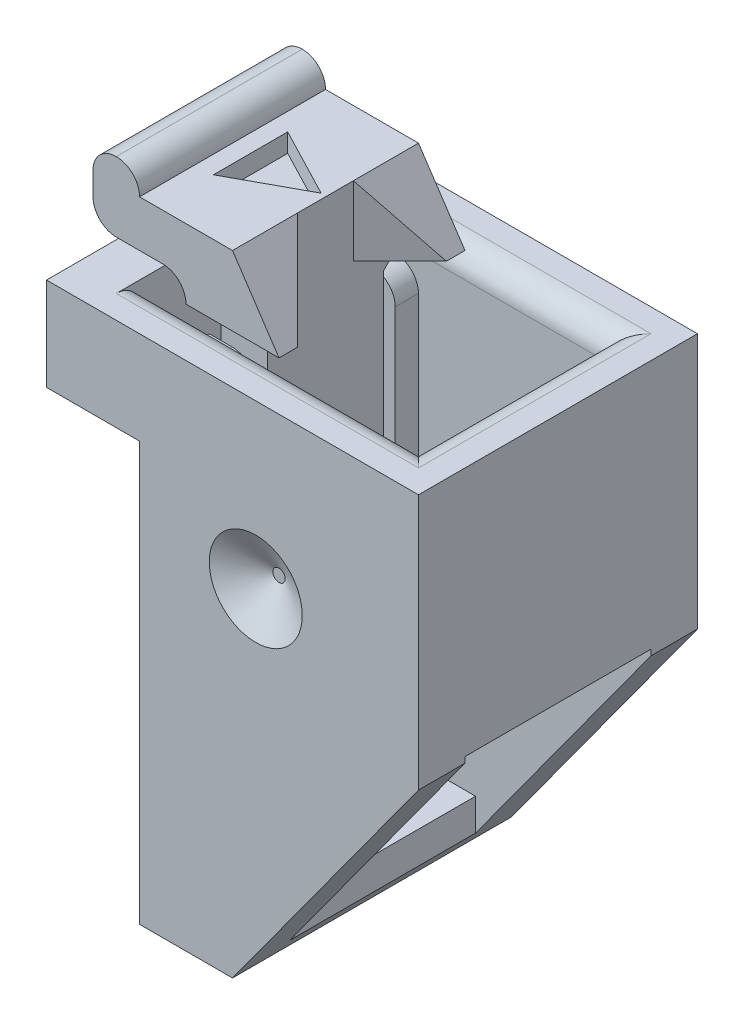
SolidWorks part; units mm, degrees
ref_plane "Front Plane" through (0, 0, 0) normal (0, 0, 1) x (1, 0, 0)
ref_plane "Top Plane" through (0, 0, 0) normal (0, 1, 0) x (1, 0, 0)
ref_plane "Right Plane" through (0, 0, 0) normal (1, 0, 0) x (0, 0, -1)
sketch "BaseSketch" plane through (0, 0, 0) normal (0, 1, 0) x (1, 0, 0)
  line L1 (-6.2677, 3.9685) -> (9.7323, 3.9685)
  line L2 (-6.2677, 3.9685) -> (-6.2677, -8.0315)
  line L3 (-6.2677, -8.0315) -> (9.7323, -8.0315)
  line L4 (9.7323, 3.9685) -> (9.7323, -8.0315)
  dimension "D1" = 16
  dimension "D2" = 12
extrude "BaseExtrude" add sketch "BaseSketch" along normal blind 2
sketch "SlotSketch" plane through (0, 2, 0) normal (0, 1, 0) x (1, 0, 0)
  line L10 (-2.2677, 0.9685) -> (-0.2677, 0.9685)
  line L11 (-2.2677, 1.9685) -> (-4.2677, 1.9685)
  line L12 (-2.2677, 1.9685) -> (-2.2677, 0.9685)
  line L13 (-0.2677, -6.0315) -> (7.7323, -6.0315)
  line L14 (7.7323, -6.0315) -> (7.7323, 1.9685)
  line L15 (-4.2677, -6.0315) -> (7.7323, -6.0315)
  line L16 (-4.2677, 1.9685) -> (-4.2677, -6.0315)
  line L17 (7.7323, 1.9685) -> (-4.2677, 1.9685)
  line L18 (7.7323, -6.0315) -> (7.7323, 1.9685)
  line L19 (-4.2677, -6.0315) -> (-2.2677, -6.0315)
  line L20 (-4.2677, 1.9685) -> (-4.2677, -6.0315)
  line L21 (7.7323, 1.9685) -> (-0.2677, 1.9685)
  line L22 (-0.2677, 1.9685) -> (-0.2677, 0.9685)
  line L23 (-2.2677, -5.0315) -> (-0.2677, -5.0315)
  line L24 (-2.2677, 0.4685) -> (-2.2677, -4.5315)
  line L25 (-2.2677, 0.4685) -> (-0.2677, 0.4685)
  line L26 (-2.2677, 0.4685) -> (-2.2677, -4.5315)
  line L27 (-2.2677, -4.5315) -> (-0.2677, -4.5315)
  line L28 (-0.2677, 0.4685) -> (-0.2677, -4.5315)
  line L29 (-0.2677, 0.4685) -> (-0.2677, -4.5315)
  line L30 (-2.2677, -5.0315) -> (-2.2677, -6.0315)
  line L31 (-0.2677, -5.0315) -> (-0.2677, -6.0315)
  line L33 (-6.2677, 3.9685) -> (9.7323, 3.9685)
  line L34 (-6.2677, 3.9685) -> (-6.2677, -8.0315)
  line L35 (-6.2677, -8.0315) -> (9.7323, -8.0315)
  line L36 (9.7323, 3.9685) -> (9.7323, -8.0315)
  line M5 (-6.2677, 3.9685) -> (-6.2677, -8.0315)
  line M6 (-6.2677, -8.0315) -> (9.7323, -8.0315)
  line M7 (9.7323, -8.0315) -> (9.7323, 3.9685)
  line M8 (9.7323, 3.9685) -> (-6.2677, 3.9685)
  dimension "D2" = 8
  dimension "D3" = 2
  dimension "D4" = 2
  dimension "D5" = 8
  dimension "D6" = 1
  dimension "D7" = 1
  dimension "D8" = 5
  dimension "D9" = 0.5
  dimension "D1" = 2
extrude "FlapExtrude" add sketch "SlotSketch" along normal blind 20.1 contours L25 L28 L27 L24
sketch "HandleBaseSketch" plane through (0, 22.1, 0) normal (0, 1, 0) x (1, 0, 0)
  line L0 (9.7323, 3.9685) -> (-6.2677, 3.9685) construction
  line L1 (-2.2677, 1.9685) -> (-0.2677, 1.9685)
  line L2 (-2.2677, 1.9685) -> (-2.2677, -6.0315)
  line L3 (-2.2677, -6.0315) -> (-0.2677, -6.0315)
  line L4 (-0.2677, 1.9685) -> (-0.2677, -6.0315)
  line L5 (-6.2677, -8.0315) -> (9.7323, -8.0315) construction
  dimension "D1" = 2
  dimension "D2" = 2
extrude "HandleBase" add sketch "HandleBaseSketch" along normal blind 3
sketch "TriangleBaseSketch" plane through (-0.2677, 0, 0) normal (1, 0, 0) x (0, 0, -1)
  line L0 (-6.0315, 22.1) -> (-3.2315, 22.1)
  line L1 (-3.2315, 22.1) -> (-3.2315, 25.1)
  line L2 (-6.0315, 25.1) -> (1.9685, 25.1) construction
  line L3 (-3.2315, 25.1) -> (-6.0315, 25.1)
  line L4 (-6.0315, 25.1) -> (-6.0315, 22.1)
  line L5 (1.9685, 22.1) -> (-0.8315, 22.1)
  line L6 (-0.8315, 22.1) -> (-0.8315, 25.1)
  line L7 (-0.8315, 25.1) -> (1.9685, 25.1)
  line L8 (1.9685, 25.1) -> (1.9685, 22.1)
extrude "PyramidExtrude" add sketch "TriangleBaseSketch" along normal blind 2.8
sketch "PyramidSideCutSketch" plane through (0, 0, -1.9685) normal (0, 0, -1) x (-1, 0, 0)
  line L0 (0.2677, 25.1) -> (0.2677, 22.1)
  line L1 (0.2677, 25.1) -> (-2.5323, 25.1)
  line L2 (-2.5323, 25.1) -> (-2.5323, 22.1)
  line L3 (-2.5323, 22.1) -> (-1.7323, 22.1)
  line L4 (-2.5323, 22.1) -> (2.2677, 22.1) construction
  line L5 (-1.7323, 22.1) -> (0.2677, 25.1)
  dimension "D1" = 2
sketch "PyramidTopCutSketch" plane through (0, 25.1, 0) normal (0, 1, 0) x (1, 0, 0)
  line L0 (-0.2677, -3.2315) -> (2.5323, -6.0315)
  line L1 (2.5323, -6.0315) -> (2.5323, -3.2315)
  line L2 (2.5323, -3.2315) -> (-0.2677, -3.2315)
  line L3 (-0.2677, -0.8315) -> (2.5323, 1.9685)
  line L4 (2.5323, 1.9685) -> (2.5323, -0.8315)
  line L5 (2.5323, -0.8315) -> (-0.2677, -0.8315)
extrude "PyramidTopCut" cut sketch "PyramidTopCutSketch" against normal blind 3
extrude "PyramidSideCut" cut sketch "PyramidSideCutSketch" against normal through all contours L1 L2 L3 L5
extrude "Boss-Extrude5" add sketch "SlotSketch<6>" along normal blind 3 contours L31 L23 L30 L19 L20 L11 L12 L10 L22 L21 L18 L13 M8 M5 M6 M7 | L12 L10 L22 L21 L18 L13 L31 L23 L30 L19 L20 L11 | L33 L36 L35 L34 region at (-1.2677, 2, -1.4685) region at (-1.2677, 2, 5.5315) region at (1.7323, 2, -3.7685)
sketch "SlotSketch<6>" plane through (0, 2, 0) normal (0, 1, 0) x (1, 0, 0) same geometry as "SlotSketch"
extrude "Sides" add sketch "SlotSketch<7>" along normal blind 20 contours L11 L20 L19 L30 L23 L31 L13 L18 L21 L22 L10 L12 | L33 L36 L35 L34
sketch "SlotSketch<7>" plane through (0, 2, 0) normal (0, 1, 0) x (1, 0, 0) same geometry as "SlotSketch"
sketch "Sketch7" plane through (-0.2677, 0, 0) normal (1, 0, 0) x (0, 0, -1)
  line L0 (-5.0315, 22) -> (-5.0315, 2) construction
  line L1 (-6.0315, 22) -> (-5.0315, 22)
  line L2 (-6.0315, 22) -> (-6.0315, 20.4974)
  line L3 (-6.0315, 20.4974) -> (-5.0315, 20.4974)
  line L4 (-5.0315, 22) -> (-5.0315, 20.4974)
  line L5 (1.9685, 22) -> (1.9685, 2) construction
  line L6 (0.9685, 22) -> (1.9685, 22)
  line L7 (0.9685, 22) -> (0.9685, 20.4974)
  line L8 (0.9685, 20.4974) -> (1.9685, 20.4974)
  line L9 (1.9685, 22) -> (1.9685, 20.4974)
extrude "WallClearanceCut" cut sketch "Sketch7" against normal blind 2
sketch "BaseTriangleCutSketch" plane through (0, 0, 8.0315) normal (0, 0, 1) x (1, 0, 0)
  line L0 (9.7323, 0) -> (1.7323, 0)
  line L1 (-6.2677, 0) -> (9.7323, 0) construction
  line L2 (1.7323, 0) -> (9.7323, 11)
  line L3 (9.7323, 22) -> (9.7323, 0) construction
  line L4 (9.7323, 11) -> (9.7323, 0)
extrude "BaseTriangleCut" cut sketch "BaseTriangleCutSketch" against normal through all
sketch "Sketch9" plane through (-2.2677, 0, 0) normal (-1, 0, 0) x (0, 0, 1)
  line L0 (6.0315, 25.1) -> (6.0315, 22.1) construction
  line L1 (-1.9685, 25.1) -> (6.0315, 25.1)
  line L2 (-1.9685, 25.1) -> (-1.9685, 23.1)
  line L3 (-1.9685, 23.1) -> (6.0315, 23.1)
  line L4 (6.0315, 25.1) -> (6.0315, 23.1)
extrude "Handle" add sketch "Sketch9" along normal blind 4
sketch "Sketch10" plane through (0, 25.1, 0) normal (0, 1, 0) x (1, 0, 0)
  line L0 (-0.2677, 1.9685) -> (-6.2677, 1.9685) construction
  line L1 (-6.2677, -6.0315) -> (-4.2659, -6.0315)
  line L2 (-6.2677, -6.0315) -> (-6.2677, 1.9685)
  line L3 (-6.2677, 1.9685) -> (-4.2659, 1.9685)
  line L4 (-4.2659, -6.0315) -> (-4.2659, 1.9685)
extrude "Boss-Extrude8" add sketch "Sketch10" along normal blind 1
sketch "WashHoleSketch" plane through (-6.2677, 0, 0) normal (-1, 0, 0) x (0, 0, 1)
  line L0 (-3.9685, 22) -> (-3.9685, 0) construction
  line L1 (-1.9685, 18) -> (6.0315, 18)
  line L2 (-1.9685, 18) -> (-1.9685, 4)
  line L3 (-1.9685, 4) -> (6.0315, 4)
  line L4 (6.0315, 18) -> (6.0315, 4)
  line L5 (8.0315, 22) -> (8.0315, 0) construction
  line L6 (-3.9685, 22) -> (8.0315, 22) construction
  line L7 (-3.9685, 0) -> (8.0315, 0) construction
  dimension "D1" = 2
  dimension "D2" = 2
  dimension "D3" = 4
  dimension "D4" = 4
extrude "WashHole" cut sketch "WashHoleSketch" against normal blind 2
fillet "Fillet1" radius 1 10 edges at (1.7323, 22, -1.9685) (1.7323, 22, 6.0315) (7.7323, 22, 2.0315) (-2.2677, 2, 2.0315) (-2.2677, 23.1, 2.0315) (-6.2677, 23.1, 2.0315) (-4.2659, 26.1, 2.0315) (-6.2677, 26.1, 2.0315) (-0.2677, 20.4974, -1.4685) (-0.2677, 20.4974, 5.5315)
sketch "MarkerSketch" plane through (0, 25.1, 0) normal (0, 1, 0) x (1, 0, 0)
  line L0 (-0.4994, -1.9893) -> (-3.4984, -0.4264)
  line L1 (-3.4984, -0.4264) -> (-3.4984, -3.6225)
  line L2 (-3.4984, -3.6225) -> (-0.4994, -1.9893)
extrude "Cut-Extrude6" cut sketch "MarkerSketch" against normal blind 0.8
sketch "Sketch11" plane through (7.7323, 0, 0) normal (-1, 0, 0) x (0, 0, 1)
  line L1 (6.0315, 8.25) -> (-1.9685, 8.25)
  line L2 (6.0315, 8.25) -> (6.0315, 11.25)
  line L3 (6.0315, 11.25) -> (-1.9685, 11.25)
  line L4 (-1.9685, 8.25) -> (-1.9685, 11.25)
  dimension "D1" = 3
extrude "Cut-Extrude7" cut sketch "Sketch11" against normal blind 10
sketch "Sketch12" plane through (0, 2, 0) normal (0, 1, 0) x (1, 0, 0)
  line L0 (-0.2677, -6.0315) -> (3.1868, -6.0315) construction
  line L1 (3.1868, 1.9685) -> (2.1868, 1.9685)
  line L2 (3.1868, 1.9685) -> (3.1868, -6.0315)
  line L3 (3.1868, -6.0315) -> (2.1868, -6.0315)
  line L4 (2.1868, 1.9685) -> (2.1868, -6.0315)
  dimension "D1" = 1
extrude "Cut-Extrude8" cut sketch "Sketch12" against normal blind 10
chamfer "Chamfer1" distance 1 angle 45 2 edges
sketch "Sketch14" plane through (0, 0, 8.0315) normal (0, 0, 1) x (1, 0, 0)
  line L0 (-6.2677, 0) -> (1.7323, 0) construction
  line L1 (-6.2677, 18) -> (-2.2677, 18)
  line L2 (-6.2677, 18) -> (-6.2677, 0)
  line L3 (-6.2677, 0) -> (-2.2677, 0)
  line L4 (-2.2677, 18) -> (-2.2677, 0)
extrude "Cut-Extrude9" cut sketch "Sketch14" against normal through all
sketch "Sketch15" plane through (0, 0, 8.0315) normal (0, 0, 1) x (1, 0, 0)
  line L0 (9.7323, 22) -> (9.7323, 11) construction
  line L1 (-6.2677, 22) -> (9.7323, 22) construction
  circle A0 centre (2.7323, 15) radius 2
  dimension "D1" = 4
  dimension "D2" = 7
  dimension "D3" = 7
extrude "Cut-Extrude10" cut sketch "Sketch15" against normal blind 1 draft 60
sketch "Sketch16" plane through (9.7323, 0, 0) normal (1, 0, 0) x (0, 0, -1)
  line L0 (-1.0315, 15.5) -> (-6.0315, 15.5)
  line L1 (-6.0315, 15.5) -> (-6.0315, 17.5)
  line L2 (-6.0315, 17.5) -> (-1.0315, 17.5)
  line L3 (-1.0315, 17.5) -> (-1.0315, 19.5)
  line L4 (-1.0315, 19.5) -> (1.9685, 16.5)
  line L5 (1.9685, 16.5) -> (-1.0315, 13.5)
  line L6 (-1.0315, 13.5) -> (-1.0315, 15.5)
  line L7 (-8.0315, 22) -> (-8.0315, 11) construction
  line L8 (3.9685, 22) -> (-8.0315, 22) construction
  point P2 (-6.0315, 16.5)
  dimension "D1" = 2
  dimension "D2" = 5
  dimension "D3" = 2
  dimension "D4" = 2
  dimension "D5" = 1
  dimension "D6" = 4.5
  dimension "D7" = 3
  dimension "D8" = 2
